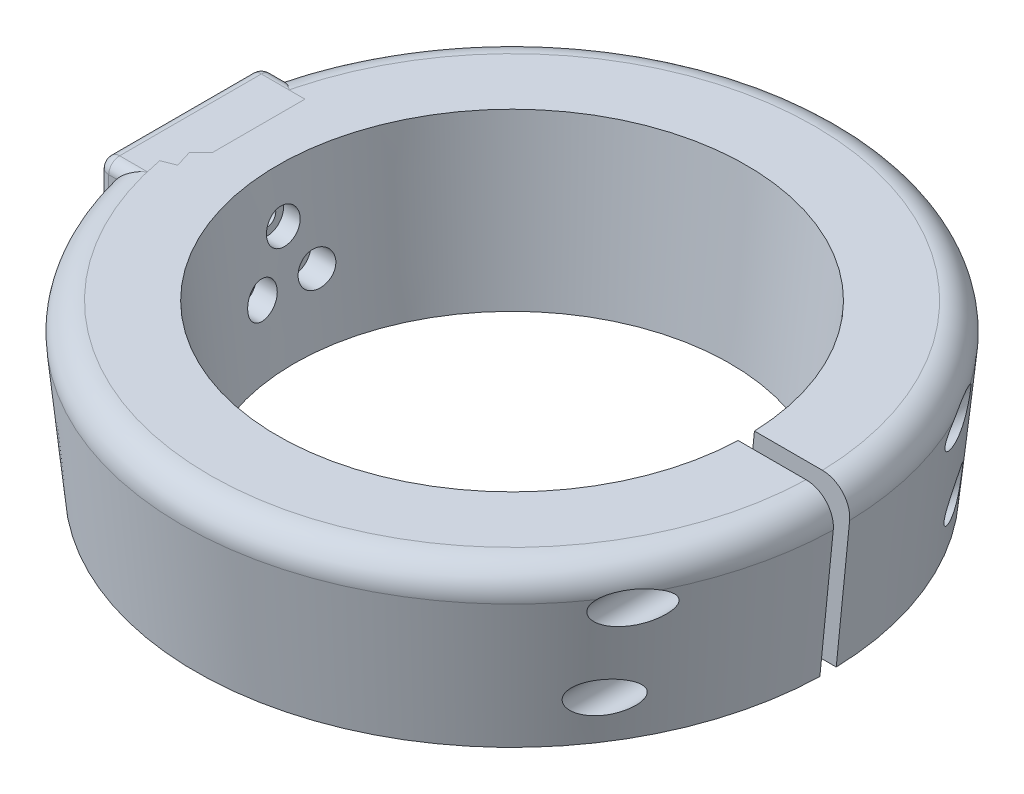
SolidWorks part; units mm, degrees
ref_plane "Front Plane" through (0, 0, 0) normal (0, 0, 1) x (1, 0, 0)
ref_plane "Top Plane" through (0, 0, 0) normal (0, 1, 0) x (1, 0, 0)
ref_plane "Right Plane" through (0, 0, 0) normal (1, 0, 0) x (0, 0, -1)
sketch "Sketch2" plane through (0, 0, 0) normal (1, 0, 0) x (0, 0, -1)
  line L0 (-58, -15) -> (-61, 15)
  line L1 (-61, 15) -> (-43, 15)
  line L2 (-43, 15) -> (-40, -15)
  line L3 (-40, -15) -> (-58, -15)
  line L4 (0, 0) -> (0, 26.5465) construction
  line L5 (-40, -15) -> (0, -15) construction
  line L6 (-43, 15) -> (0, 15) construction
  point P7 (-41.5, 0)
  point P8 (0, 0)
  dimension "D1" = 18
  dimension "D2" = 40
  dimension "D3" = 43
  dimension "D4" = 18
  dimension "D5" = 30
revolve "Revolve1" add sketch "Sketch2" angle 360 mid plane about L4
sketch "Sketch3" plane through (0, 15, 0) normal (0, 1, 0) x (1, 0, 0)
  line L1 (113.6586, -1.5) -> (28.0764, -1.5)
  line L2 (113.6586, -1.5) -> (113.6586, 1.5)
  line L3 (113.6586, 1.5) -> (28.0764, 1.5)
  line L4 (28.0764, -1.5) -> (28.0764, 1.5)
  line L5 (113.6586, -1.5) -> (28.0764, 1.5) construction
  line L6 (113.6586, 1.5) -> (28.0764, -1.5) construction
  point P0 (70.8675, 0)
  point P5 (0, 0)
  dimension "D1" = 3
extrude "Cut-Extrude1" cut sketch "Sketch3" against normal through all
sketch "Sketch4" plane through (0, 0, 0) normal (0, 0, 1) x (1, 0, 0)
  line L0 (51.9777, 7.3483) -> (48.9762, -7.3483) construction
  line L1 (60.9816, 15) -> (42.9738, 15) construction
  line L2 (57.9806, -15) -> (39.9719, -15) construction
  circle A0 centre (51.9777, 7.3483) radius 1.65
  circle A1 centre (48.9762, -7.3483) radius 1.65
  point P6 (0, 0)
  point P7 (51.9777, 15)
  point P8 (50.477, 0)
  point P12 (44.6166, -7.4067)
  point P13 (0, 0)
  point P16 (48.9762, -15)
  dimension "D1" = 3.3
  dimension "D2" = 15
extrude "Cut-Extrude2" cut sketch "Sketch4" against normal through all
ref_plane "Plane1" through (0, 0, -11.5) normal (0, 0, 1) x (1, 0, 0)
sketch "Sketch6" plane through (0, 0, -11.5) normal (0, 0, 1) x (1, 0, 0)
  circle A0 centre (51.9777, 7.3483) radius 3.075
  circle A1 centre (48.9762, -7.3483) radius 3.075
  dimension "D1" = 6.15
extrude "Cut-Extrude3" cut sketch "Sketch6" against normal through all
mirror "Mirror1" about plane through (0, 0, 0) normal (0, 0, 1) of "Cut-Extrude3"
sketch "Sketch7" plane through (0, 0, 1.5) normal (0, 0, -1) x (-1, 0, 0)
  circle A0 centre (-51.9777, 7.3483) radius 2.125
  circle A1 centre (-48.9762, -7.3483) radius 2.125
  dimension "D1" = 4.25
extrude "Cut-Extrude4" cut sketch "Sketch7" against normal through all
sketch "Sketch8" plane through (0, 0, 0) normal (0, 0, 1) x (1, 0, 0)
  line L0 (-61, 15) -> (-61, -15)
  line L2 (-61, -15) -> (-51, -15)
  line L4 (0, 0) -> (0, 26.5465) construction
  line L5 (0, 0) -> (0, 26.5465) construction
  line L6 (-58, -15) -> (57.9806, -15) construction
  line L7 (-51, -15) -> (-51, 15)
  line L8 (-51, 15) -> (-61, 15)
  dimension "D1" = 10
extrude "Boss-Extrude1" add sketch "Sketch8" along normal mid plane 30 separate body
sketch "Sketch9" plane through (-61, 0, 0) normal (-1, 0, 0) x (0, 0, 1)
  line L0 (0, 0) -> (0, 26.5465) construction
  line L1 (0, 5.7735) -> (-5, -2.8868) construction
  line L2 (-5, -2.8868) -> (5, -2.8868) construction
  line L3 (5, -2.8868) -> (0, 5.7735) construction
  line L4 (-2.5, 1.4434) -> (5, -2.8868) construction
  line L5 (5, -2.8868) -> (2.5, 1.4434) construction
  line L6 (2.5, 1.4434) -> (-5, -2.8868) construction
  line L7 (15, 15) -> (15, -15) construction
  circle A0 centre (0, 5.7735) radius 1.65
  circle A1 centre (5, -2.8868) radius 1.65
  circle A2 centre (-5, -2.8868) radius 1.65
  point P9 (0, 0)
  point P11 (0, 0)
  point P12 (0, -2.5318)
  point P13 (0, 0)
  point P14 (5, 3.4915)
  point P16 (0, -0.1704)
  point P17 (2.5, 10.7155)
  point P18 (0, 0)
  point P20 (0, 0)
  point P21 (15, 0)
  dimension "D2" = 3.3
  dimension "D1" = 10
extrude "Cut-Extrude5" cut sketch "Sketch9" against normal blind 30
sketch "Sketch10" plane through (0, 0, 0) normal (1, 0, 0) x (0, 0, -1)
  circle A0 centre (5, -2.8868) radius 3.075
  circle A1 centre (-5, -2.8868) radius 3.075
  circle A2 centre (0, 5.7735) radius 3.075
  point P7 (0, 5.7735)
  point P9 (4.8866, -3.0301)
  point P10 (4.8929, -3.0397)
  point P11 (5, -2.8868)
  dimension "D1" = 6.15
extrude "Cut-Extrude6" cut sketch "Sketch10" against normal blind 45
fillet "Fillet1" radius 5 1 edges at (-61, 15, 0)
fillet "Fillet2" radius 2 6 edges at (-56, 15, 15) (-56, 15, -15) (-61, -15, 0) (-61, 0, -15) (-61, 0, 15) (-61, 15, 0)
